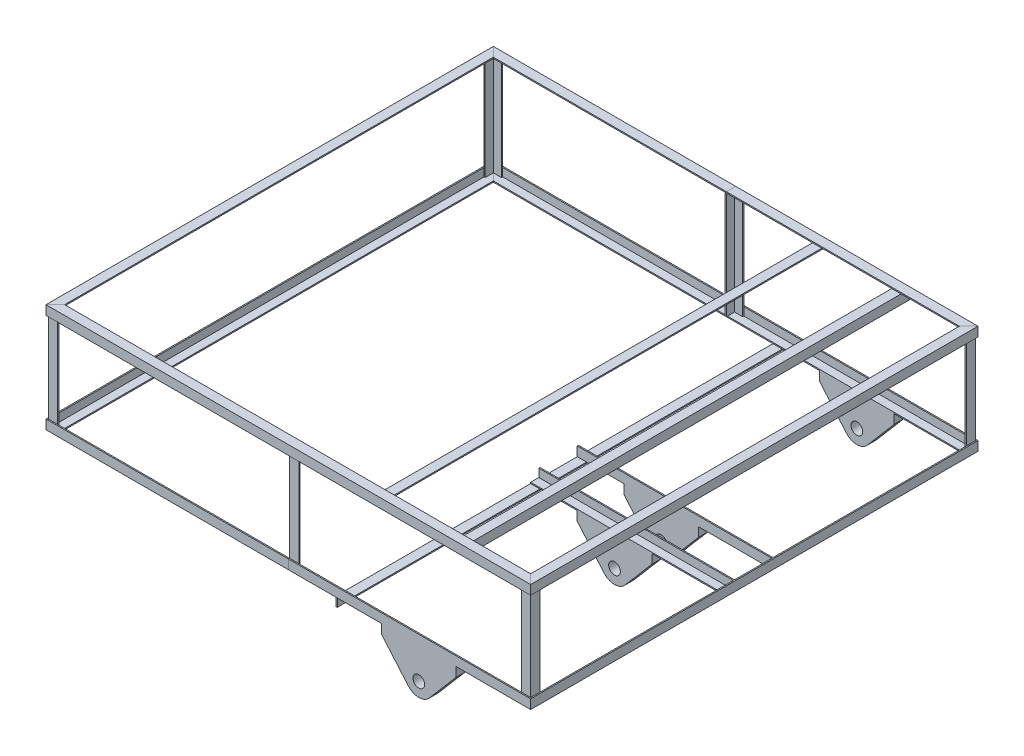
SolidWorks part; units mm, degrees
ref_plane "Front Plane" through (0, 0, 0) normal (0, 0, 1) x (1, 0, 0)
ref_plane "Top Plane" through (0, 0, 0) normal (0, 1, 0) x (1, 0, 0)
ref_plane "Right Plane" through (0, 0, 0) normal (1, 0, 0) x (0, 0, -1)
sketch "Sketch1" plane through (0, 0, 0) normal (0, 1, 0) x (1, 0, 0)
  line L1 (-330.2, -304.8) -> (330.2, -304.8)
  line L2 (-330.2, -304.8) -> (-330.2, 304.8)
  line L3 (-330.2, 304.8) -> (330.2, 304.8)
  line L4 (330.2, -304.8) -> (330.2, 304.8)
  line L5 (-330.2, -304.8) -> (330.2, 304.8) construction
  line L6 (-330.2, 304.8) -> (330.2, -304.8) construction
  point P0 (0, 0)
  dimension "D1" = 660.4
  dimension "D2" = 609.6
sketch "Sketch2" plane through (0, 0, 0) normal (1, 0, 0) x (0, 0, -1)
  line L0 (-304.8, 0) -> (-292.1, 0)
  line L1 (304.8, 0) -> (-304.8, 0) construction
  line L2 (-304.8, 0) -> (304.8, 0) construction
  line L3 (-292.1, 0) -> (-292.1, 1.5875)
  line L4 (-292.1, 1.5875) -> (-303.2125, 1.5875)
  line L5 (-303.2125, 1.5875) -> (-303.2125, 12.7)
  line L6 (-303.2125, 12.7) -> (-304.8, 12.7)
  line L7 (-304.8, 12.7) -> (-304.8, 0)
  dimension "D1" = 1.5875
  dimension "D2" = 12.7
sweep "Sweep1" add profiles "Sketch2" path "Sketch1"
sketch "Sketch3" plane through (0, 0, 0) normal (0, 0, 1) x (1, 0, 0)
  line L0 (-330.2, 12.7) -> (-330.2, 0) construction
  line L1 (-330.2, -144.4625) -> (330.2, -144.4625)
  line L2 (-330.2, -144.4625) -> (-330.2, 147.6375)
  line L3 (-330.2, 147.6375) -> (330.2, 147.6375)
  line L4 (330.2, -144.4625) -> (330.2, 147.6375)
  line L5 (-330.2, -144.4625) -> (330.2, 147.6375) construction
  line L6 (-330.2, 147.6375) -> (330.2, -144.4625) construction
  line L7 (0, 0) -> (330.2, 0) construction
  point P0 (0, 1.5875)
  dimension "D1" = 292.1
  dimension "D2" = 144.4625
ref_plane "Plane1" through (0, 147.6375, 0) normal (0, 1, 0) x (1, 0, 0)
sketch "Sketch4" plane through (0, 147.6375, 0) normal (0, 1, 0) x (1, 0, 0)
  line L1 (-330.2, -304.8) -> (330.2, -304.8)
  line L2 (-330.2, -304.8) -> (-330.2, 304.8)
  line L3 (-330.2, 304.8) -> (330.2, 304.8)
  line L4 (330.2, -304.8) -> (330.2, 304.8)
  line L5 (-330.2, -304.8) -> (330.2, 304.8) construction
  line L6 (-330.2, 304.8) -> (330.2, -304.8) construction
sketch "Sketch5" plane through (0, 0, 0) normal (1, 0, 0) x (0, 0, -1)
  line L0 (304.8, 147.6375) -> (304.8, 134.9375)
  line L1 (304.8, 147.6375) -> (-304.8, 147.6375) construction
  line L2 (-304.8, 147.6375) -> (304.8, 147.6375) construction
  line L3 (304.8, 134.9375) -> (303.2125, 134.9375)
  line L4 (303.2125, 134.9375) -> (303.2125, 146.05)
  line L5 (303.2125, 146.05) -> (292.1, 146.05)
  line L6 (292.1, 146.05) -> (292.1, 147.6375)
  line L7 (292.1, 147.6375) -> (304.8, 147.6375)
  dimension "D1" = 1.5875
  dimension "D2" = 12.7
sweep "Sweep2" add profiles "Sketch5" path "Sketch4"
sketch "Sketch6" plane through (0, 1.5875, 0) normal (0, 1, 0) x (1, 0, 0)
  line L0 (-328.6125, -290.5125) -> (-328.6125, -303.2125)
  line L1 (-328.6125, 303.2125) -> (-328.6125, -303.2125) construction
  line L2 (-328.6125, -303.2125) -> (-315.9125, -303.2125)
  line L3 (-328.6125, -303.2125) -> (0, -303.2125) construction
  line L4 (-315.9125, -303.2125) -> (-315.9125, -301.625)
  line L5 (-315.9125, -301.625) -> (-327.025, -301.625)
  line L6 (-328.6125, -303.2125) -> (-317.5, -292.1) construction
  line L7 (-327.025, -301.625) -> (-327.025, -290.5125)
  line L8 (-327.025, -290.5125) -> (-328.6125, -290.5125)
  line L10 (-328.6125, -303.2125) -> (328.6125, -303.2125) construction
  line L12 (0, -303.2125) -> (328.6125, -303.2125) construction
  line L17 (315.9125, -303.2125) -> (328.6125, -303.2125)
  line L18 (328.6125, -303.2125) -> (328.6125, -290.5125)
  line L19 (328.6125, -303.2125) -> (328.6125, 303.2125) construction
  line L20 (328.6125, -290.5125) -> (327.025, -290.5125)
  line L21 (327.025, -290.5125) -> (327.025, -301.625)
  line L22 (328.6125, -303.2125) -> (317.5, -292.1) construction
  line L23 (327.025, -301.625) -> (315.9125, -301.625)
  line L24 (315.9125, -301.625) -> (315.9125, -303.2125)
  line L27 (0, -303.2125) -> (12.7, -303.2125) construction
  line L28 (12.7, -303.2125) -> (12.7, -301.625)
  line L29 (12.7, -301.625) -> (1.5875, -301.625)
  line L30 (1.5875, -301.625) -> (1.5875, -290.5125)
  line L31 (1.5875, -290.5125) -> (0, -290.5125)
  line L32 (0, -290.5125) -> (0, -303.2125)
  line L33 (0, -303.2125) -> (12.7, -303.2125)
  point P8 (0, 0)
  point P22 (0, -303.2125)
  dimension "D1" = 12.7
  dimension "D2" = 1.5875
  dimension "D3" = 12.7
  dimension "D4" = 1.5875
  dimension "D5" = 12.7
  dimension "D6" = 1.5875
extrude "Boss-Extrude4" add sketch "Sketch6" along normal up to surface (144.4625 mm away) up to face at (0, 146.05, 297.6562)
mirror "Mirror1" about plane through (0, 0, 0) normal (0, 0, 1) of "Boss-Extrude4"
sketch "Sketch7" plane through (0, 0, 303.2125) normal (0, 0, -1) x (-1, 0, 0)
  line L29 (-238.125, 146.05) -> (-238.125, 133.35)
  line L30 (-315.9125, 146.05) -> (-12.7, 146.05) construction
  line L31 (-238.125, 133.35) -> (-236.5375, 133.35)
  line L32 (-236.5375, 133.35) -> (-236.5375, 144.4625)
  line L33 (-236.5375, 144.4625) -> (-225.425, 144.4625)
  line L48 (-225.425, 144.4625) -> (-225.425, 146.05)
  line L49 (-225.425, 146.05) -> (-238.125, 146.05)
  line L50 (-130.175, 146.05) -> (-117.475, 146.05)
  line L51 (-117.475, 146.05) -> (-117.475, 133.35)
  line L52 (-117.475, 133.35) -> (-119.0625, 133.35)
  line L53 (-119.0625, 133.35) -> (-119.0625, 144.4625)
  line L54 (-119.0625, 144.4625) -> (-130.175, 144.4625)
  line L55 (-130.175, 144.4625) -> (-130.175, 146.05)
  line L57 (-225.425, 146.05) -> (-130.175, 146.05) construction
  line L59 (-330.2, 0) -> (330.2, 0) construction
  line L65 (-76.2, 0) -> (-76.2, -1.5875)
  line L66 (-76.2, -1.5875) -> (-65.0875, -1.5875)
  line L67 (-65.0875, -1.5875) -> (-65.0875, -12.7)
  line L68 (-65.0875, -12.7) -> (-63.5, -12.7)
  line L69 (-63.5, -12.7) -> (-63.5, 0)
  line L70 (-63.5, 0) -> (-76.2, 0)
  line L71 (-76.2, 0) -> (-279.4, 0) construction
  line L72 (-330.2, 134.9375) -> (-330.2, 147.6375) construction
  point P13 (-177.8, 146.05)
  point P15 (-283.6531, 0)
  point P20 (-177.8, 0)
  dimension "D1" = 12.7
  dimension "D2" = 1.5875
  dimension "D3" = 117.475
  dimension "D4" = 203.2
  dimension "D5" = 152.4
extrude "Boss-Extrude5" add sketch "Sketch7" along normal up to surface (606.425 mm away) up to face at (-157.9562, 140.4937, -303.2125)
sketch "Sketch8" plane through (0, 0, 0) normal (0, 0, 1) x (1, 0, 0)
  line L0 (236.5375, 144.4625) -> (119.0625, 144.4625) construction
  line L1 (177.8, 144.4625) -> (177.8, -42.8625) construction
  line L2 (-330.2, 0) -> (0, 0) construction
  line L3 (127, -12.7) -> (127, 0)
  line L4 (127, 0) -> (228.6, 0)
  line L5 (228.6, 0) -> (228.6, -12.7)
  line L6 (228.6, -12.7) -> (192.288, -55.2318)
  line L7 (127, -12.7) -> (163.312, -55.2318)
  line L8 (330.2, 0) -> (-330.2, 0) construction
  circle A0 centre (177.8, -42.8625) radius 7.9375
  arc A2 (163.312, -55.2318) -> (192.288, -55.2318) centre (177.8, -42.8625) ccw
  point P12 (149.8319, 19.2016)
  point P17 (177.8, 0)
  dimension "D2" = 15.875
  dimension "D3" = 101.6
  dimension "D4" = 38.1
  dimension "D1" = 42.8625
  dimension "D5" = 12.7
extrude "Boss-Extrude6" add sketch "Sketch8" against normal blind 12.7 from surface starting at face at (-165.1, 6.35, 304.8)
sketch "Sketch11" plane through (0, 0, -304.8) normal (0, 0, -1) x (-1, 0, 0)
  line L3 (-127, -12.7) -> (-127, 0)
  line L4 (-127, 0) -> (-228.6, 0)
  line L5 (-228.6, 0) -> (-228.6, -12.7)
  line L6 (-127, -12.7) -> (-127, 0)
  line L7 (-127, 0) -> (-228.6, 0)
  line L8 (-228.6, 0) -> (-228.6, -12.7)
  line L11 (-228.6, -12.7) -> (-192.288, -55.2318)
  line L12 (-228.6, -12.7) -> (-192.288, -55.2318)
  line L13 (-163.312, -55.2318) -> (-127, -12.7)
  line L14 (-163.312, -55.2318) -> (-127, -12.7)
  circle A1 centre (-177.8, -42.8625) radius 7.9375
  circle A2 centre (-177.8, -42.8625) radius 7.9375
  arc A3 (-192.288, -55.2318) -> (-163.312, -55.2318) centre (-177.8, -42.8625) ccw
  arc A5 (-192.288, -55.2318) -> (-163.312, -55.2318) centre (-177.8, -42.8625) ccw
  dimension "D1" = 0
  dimension "D2" = 0
extrude "Boss-Extrude11" add sketch "Sketch11" against normal up to surface (12.7 mm away) up to face at (17.6609, 0.7938, -292.1)
sketch "Sketch12" plane through (63.5, 0, 0) normal (-1, 0, 0) x (0, 0, 1)
  line L0 (-25.4, 0) -> (-25.4, 12.7)
  line L1 (-292.1, 0) -> (292.1, 0) construction
  line L2 (-25.4, 12.7) -> (-26.9875, 12.7)
  line L3 (-26.9875, 12.7) -> (-26.9875, 1.5875)
  line L4 (-26.9875, 1.5875) -> (-38.1, 1.5875)
  line L5 (-38.1, 1.5875) -> (-38.1, 0)
  line L6 (-38.1, 0) -> (-25.4, 0)
  line L7 (25.4, 0) -> (25.4, 12.7)
  line L8 (25.4, 12.7) -> (26.9875, 12.7)
  line L9 (26.9875, 12.7) -> (26.9875, 1.5875)
  line L10 (26.9875, 1.5875) -> (38.1, 1.5875)
  line L11 (38.1, 1.5875) -> (38.1, 0)
  line L12 (38.1, 0) -> (25.4, 0)
  line L13 (-25.4, 0) -> (25.4, 0) construction
  point P10 (0, 0)
  dimension "D1" = 1.5875
  dimension "D2" = 12.7
  dimension "D3" = 50.8
extrude "Boss-Extrude12" add sketch "Sketch12" against normal up to surface (265.1125 mm away) up to face at (328.6125, 7.1438, 0)
sketch "Sketch13" plane through (0, 0, -38.1) normal (0, 0, -1) x (-1, 0, 0)
  line L21 (-1.5875, 1.5875) -> (-317.5, 1.5875)
  line L22 (0, 1.5875) -> (-1.5875, 1.5875)
  line L23 (317.5, 1.5875) -> (0, 1.5875)
  line L24 (317.5, 0) -> (317.5, 1.5875)
  line L25 (-63.5, 0) -> (317.5, 0)
  line L26 (-76.2, 0) -> (-63.5, 0)
  line L27 (-127, 0) -> (-76.2, 0)
  line L28 (-127, -12.7) -> (-127, 0)
  line L29 (-163.312, -55.2318) -> (-127, -12.7)
  line L30 (-228.6, -12.7) -> (-192.288, -55.2318)
  line L31 (-228.6, 0) -> (-228.6, -12.7)
  line L32 (-317.5, 0) -> (-228.6, 0)
  line L35 (-317.5, 1.5875) -> (-317.5, 0)
  line L39 (317.5, 0) -> (317.5, 1.5875)
  line L40 (-63.5, 0) -> (317.5, 0)
  line L41 (-76.2, 0) -> (-63.5, 0)
  line L50 (-317.5, 1.5875) -> (-317.5, 0)
  line L51 (-127, -12.7) -> (-127, 0) construction
  line L52 (-163.312, -55.2318) -> (-127, -12.7) construction
  line L53 (-228.6, -12.7) -> (-192.288, -55.2318) construction
  line L54 (-228.6, 0) -> (-228.6, -12.7) construction
  line L55 (-127, -12.7) -> (-127, 0)
  line L56 (-163.312, -55.2318) -> (-127, -12.7)
  line L57 (-228.6, -12.7) -> (-192.288, -55.2318)
  line L58 (-228.6, 0) -> (-228.6, -12.7)
  line L59 (-127, 0) -> (-228.6, 0)
  arc A5 (-192.288, -55.2318) -> (-163.312, -55.2318) centre (-177.8, -42.8625) ccw
  circle A7 centre (-177.8, -42.8625) radius 7.9375 construction
  arc A8 (-192.288, -55.2318) -> (-163.312, -55.2318) centre (-177.8, -42.8625) ccw construction
  circle A9 centre (-177.8, -42.8625) radius 7.9375
  arc A10 (-192.288, -55.2318) -> (-163.312, -55.2318) centre (-177.8, -42.8625) ccw
  line M3 (-317.5, 0) -> (-76.2, 0)
  dimension "D1" = 0
sketch "Sketch14" plane through (0, 0, 38.1) normal (0, 0, 1) x (1, 0, 0)
  line L0 (228.6, 0) -> (228.6, -12.7) construction
  line L1 (127, -12.7) -> (127, 0) construction
  line L2 (127, 0) -> (228.6, 0) construction
  line L3 (228.6, 0) -> (228.6, -12.7)
  line L4 (127, -12.7) -> (127, 0)
  line L5 (127, 0) -> (228.6, 0)
  line L6 (317.5, 0) -> (317.5, 1.5875)
  line L7 (317.5, 1.5875) -> (63.5, 1.5875)
  line L8 (63.5, 1.5875) -> (63.5, 0)
  line L9 (63.5, 0) -> (76.2, 0)
  line L10 (76.2, 0) -> (317.5, 0)
  line L11 (317.5, 0) -> (317.5, 1.5875)
  line L13 (317.5, 1.5875) -> (63.5, 1.5875)
  line L14 (63.5, 1.5875) -> (63.5, 0)
  line L15 (63.5, 0) -> (76.2, 0)
  line L16 (76.2, 0) -> (317.5, 0)
  line L18 (163.312, -55.2318) -> (127, -12.7) construction
  line L19 (228.6, -12.7) -> (192.288, -55.2318) construction
  line L20 (163.312, -55.2318) -> (127, -12.7)
  line L21 (228.6, -12.7) -> (192.288, -55.2318)
  circle A1 centre (177.8, -42.8625) radius 7.9375 construction
  circle A3 centre (177.8, -42.8625) radius 7.9375
  circle A4 centre (177.8, -42.8625) radius 7.9375 construction
  arc A5 (163.312, -55.2318) -> (192.288, -55.2318) centre (177.8, -42.8625) ccw construction
  circle A6 centre (177.8, -42.8625) radius 7.9375
  arc A7 (163.312, -55.2318) -> (192.288, -55.2318) centre (177.8, -42.8625) ccw
  line M11 (76.2, 0) -> (317.5, 0)
  dimension "D1" = 0
extrude "Boss-Extrude15" add sketch "Sketch13" against normal up to surface (12.7 mm away) contours L57 A10 L56 L55 L58 A9 M3 region at (177.8, -22.6962, -38.1) up to face at (213.6321, 4.0821, -25.4)
extrude "Boss-Extrude16" add sketch "Sketch14" against normal up to surface (12.7 mm away) contours L20 A7 L21 L3 L4 A3 M11 region at (177.8, -22.6962, 38.1) up to face at (213.6321, 4.0821, 25.4)
